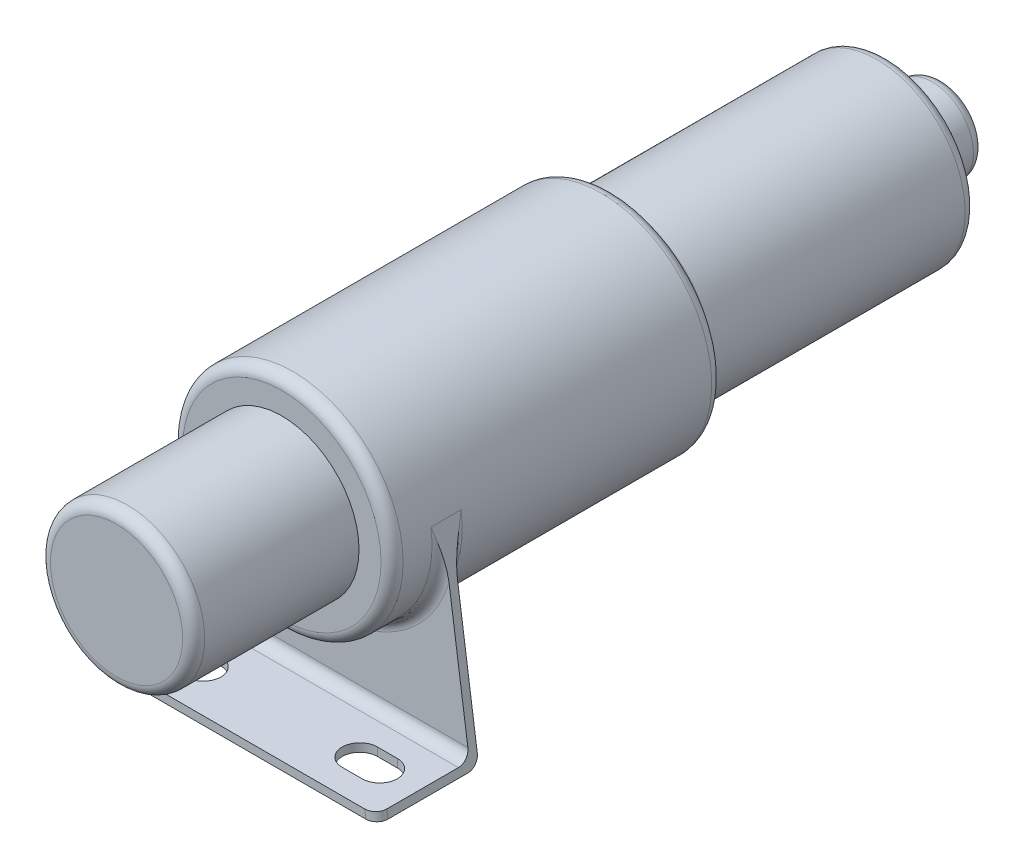
SolidWorks part; units mm, degrees
ref_plane "Front Plane" through (0, 0, 0) normal (0, 0, 1) x (1, 0, 0)
ref_plane "Top Plane" through (0, 0, 0) normal (0, 1, 0) x (1, 0, 0)
ref_plane "Right Plane" through (0, 0, 0) normal (1, 0, 0) x (0, 0, -1)
sketch "Sketch1" plane through (0, 0, 0) normal (0, 0, 1) x (1, 0, 0)
  circle A0 centre (0, 0) radius 20
  dimension "D1" = 40
extrude "Boss-Extrude1" add sketch "Sketch1" along normal mid plane 150
sketch "Sketch2" plane through (0, 0, 75) normal (0, 0, 1) x (1, 0, 0)
  circle A0 centre (0, 0) radius 14
  circle A1 centre (0, 0) radius 20
  circle A2 centre (0, 0) radius 20 construction
  dimension "D1" = 28
extrude "Cut-Extrude1" cut sketch "Sketch2" against normal blind 30
sketch "Sketch3" plane through (0, 0, 45) normal (0, 0, 1) x (1, 0, 0)
  line L0 (-19.8035, 2.7967) -> (-25, -34)
  line L1 (19.8035, 2.7967) -> (25, -34)
  line L2 (25, -34) -> (-25, -34)
  arc A0 (-19.8035, 2.7967) -> (19.8035, 2.7967) centre (0, 0) ccw
  circle A1 centre (0, 0) radius 20 construction
  point P14 (0, -20)
  dimension "D1" = 50
  dimension "D2" = 14
extrude "Boss-Extrude2" add sketch "Sketch3" against normal mid plane 1.5 from offset 10 offset against normal yes
sketch "Sketch4" plane through (0, 0, 35.75) normal (0, 0, 1) x (1, 0, 0)
  line L0 (-25, -34) -> (-24.7882, -32.5)
  line L1 (-19.8035, 2.7967) -> (-25, -34) construction
  line L2 (-24.7882, -32.5) -> (24.7882, -32.5)
  line L3 (25, -34) -> (19.8035, 2.7967) construction
  line L4 (24.7882, -32.5) -> (25, -34)
  line L5 (25, -34) -> (-25, -34)
  dimension "D1" = 1.5
extrude "Boss-Extrude3" add sketch "Sketch4" along normal blind 17
sketch "Sketch5" plane through (0, -34, 0) normal (0, -1, 0) x (-1, 0, 0)
  line L0 (16, -48.25) -> (-16, -48.25) construction
  line L1 (25, -52.75) -> (-25, -52.75) construction
  line L2 (17.8, -45.05) -> (14.2, -45.05) construction
  line L3 (17.8, -48.25) -> (14.2, -48.25)
  line L4 (17.8, -41.85) -> (14.2, -41.85)
  line L5 (0, -52.75) -> (0, -34.25) construction
  line L6 (20, -34.25) -> (-20, -34.25) construction
  line L7 (-17.8, -45.05) -> (-14.2, -45.05) construction
  line L8 (-17.8, -48.25) -> (-14.2, -48.25)
  line L9 (-17.8, -41.85) -> (-14.2, -41.85)
  arc A0 (17.8, -48.25) -> (17.8, -41.85) centre (17.8, -45.05) ccw
  arc A1 (14.2, -41.85) -> (14.2, -48.25) centre (14.2, -45.05) ccw
  arc A2 (-17.8, -48.25) -> (-17.8, -41.85) centre (-17.8, -45.05) cw
  arc A3 (-14.2, -41.85) -> (-14.2, -48.25) centre (-14.2, -45.05) cw
  point P2 (0, -48.25)
  point P8 (16, -45.05)
  point P13 (11, -45.05)
  point P17 (21, -45.05)
  point P21 (-16, -45.05)
  dimension "D1" = 4.5
  dimension "D2" = 32
  dimension "D3" = 6.4
  dimension "D4" = 10
extrude "Cut-Extrude2" cut sketch "Sketch5" against normal up to next
ref_axis "Axis1" through (0, 0, 45) along (0, 0, -1)
sketch "Sketch6" plane through (0, 0, 0) normal (1, 0, 0) x (0, 0, -1)
  line L0 (15, 20) -> (15, 16)
  line L1 (75, 20) -> (-45, 20) construction
  line L2 (15, 16) -> (65, 16)
  line L3 (65, 16) -> (65, 7.5)
  line L4 (65, 7.5) -> (75, 7.5)
  line L5 (75, -20) -> (75, 20) construction
  line L6 (75, 7.5) -> (75, -7.5) construction
  line L7 (15, 20) -> (75, 20)
  line L8 (75, 20) -> (75, 7.5)
  point P6 (75, 0)
  point P11 (75, 20)
  dimension "D1" = 10
  dimension "D2" = 15
  dimension "D3" = 50
  dimension "D4" = 4
revolve "Cut-Revolve1" cut sketch "Sketch6" angle 360 about axis through (0, 0, 45) along (0, 0, -1)
fillet "Fillet1" radius 2 13 edges at (14, 0, 75) (0, -20, 34.25) (0, -20, 35.75) (0, -34, 34.25) (0, -32.5, 35.75) (-24.8941, -33.25, 52.75) (24.8941, -33.25, 52.75) (20, 0, 45) (7.5, 0, -75) (7.5, 0, -65) (16, 0, -65) (20, 0, -15) (16, 0, -15)
